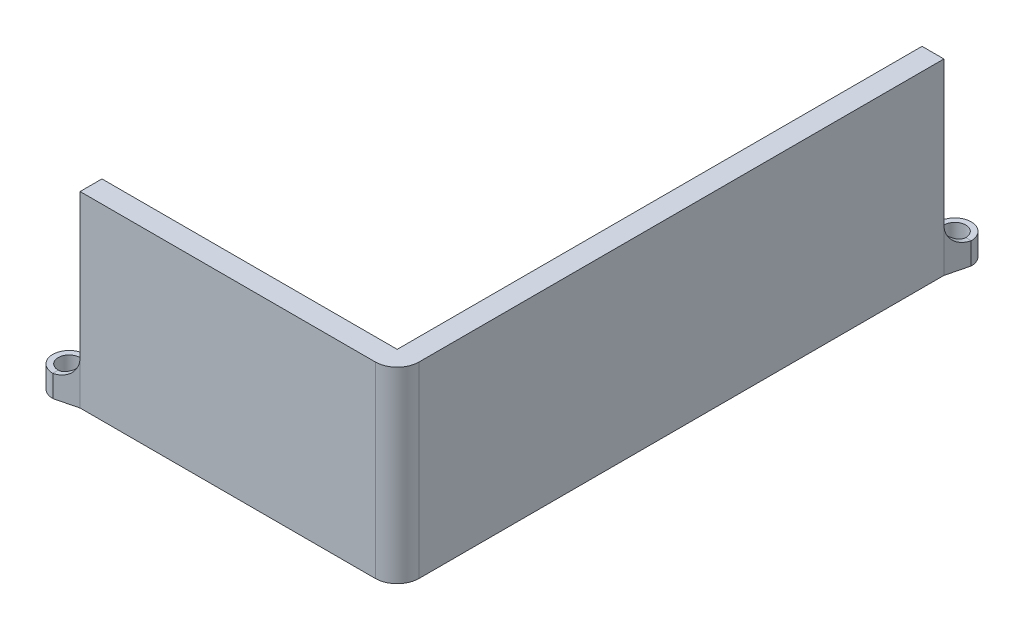
SolidWorks part; units mm, degrees
ref_plane "Front Plane" through (0, 0, 0) normal (0, 0, 1) x (1, 0, 0)
ref_plane "Top Plane" through (0, 0, 0) normal (0, 1, 0) x (1, 0, 0)
ref_plane "Right Plane" through (0, 0, 0) normal (1, 0, 0) x (0, 0, -1)
other "Configuration Table"
sketch "Sketch2" plane through (0, 0, 0) normal (0, 0, 1) x (1, 0, 0)
  line L1 (-13.6181, -8.5) -> (13.3819, -8.5)
  line L2 (-13.6181, -8.5) -> (-13.6181, 8.65)
  line L3 (-13.6181, 8.65) -> (13.3819, 8.65)
  line L4 (13.3819, -8.5) -> (13.3819, 8.65)
  line L5 (11.5, -8.5) -> (-11.5, -8.5) construction
  line L6 (-11.5, 8.5) -> (11.5, 8.5) construction
  line L7 (-13.6181, 8.65) -> (13.3819, -8.5) construction
  point P0 (0, 0)
  dimension "D1" = 27
  dimension "D2" = 0.15
extrude "Boss-Extrude1" add sketch "Sketch2" along normal blind 2
sketch "Sketch3" plane through (13.3819, 0, 0) normal (1, 0, 0) x (0, 0, -1)
  line L1 (-2, 8.65) -> (48, 8.65)
  line L2 (-2, 8.65) -> (-2, -8.5)
  line L3 (-2, -8.5) -> (48, -8.5)
  line L4 (48, 8.65) -> (48, -8.5)
  line L5 (-2, -8.5) -> (0, -8.5) construction
  line L6 (-2, -8.5) -> (0, -8.5)
  line M3 (0, -8.5) -> (0, 8.65)
  line M4 (0, 8.65) -> (-2, 8.65)
  line M5 (-2, 8.65) -> (-2, -8.5)
  line M6 (-2, -8.5) -> (0, -8.5)
  dimension "D1" = 50
extrude "Boss-Extrude2" add sketch "Sketch3" along normal blind 2 contours L4 L1 L3 M3 | M6 M3 M4 M5 region at (13.3819, 0.075, 1) region at (13.3819, 0.075, -24)
fillet "Fillet1" radius 2 1 edges at (15.3819, 0.075, 2)
sketch "Sketch4" plane through (0, -8.5, 0) normal (0, -1, 0) x (1, 0, 0)
  line L0 (14.3819, -48) -> (14.3819, -50) construction
  line L1 (12.8819, -50) -> (13.3819, -48)
  line L2 (15.8819, -50) -> (15.3819, -48)
  line L3 (-15.6181, -0.5) -> (-13.6181, 0)
  line L4 (-15.6181, 2.5) -> (-13.6181, 2)
  line L5 (-15.6181, 1) -> (-13.6181, 1) construction
  line L6 (15.3819, -48) -> (15.3819, 0)
  line L7 (13.3819, 2) -> (-13.6181, 2)
  line L8 (-13.6181, 2) -> (-13.6181, 0)
  line L9 (-13.6181, 0) -> (13.3819, 0)
  line L10 (13.3819, 0) -> (13.3819, -48)
  line L11 (13.3819, -48) -> (15.3819, -48)
  line L12 (15.3819, -48) -> (15.3819, 0)
  line L13 (13.3819, 2) -> (-13.6181, 2)
  line L14 (-13.6181, 2) -> (-13.6181, 0)
  line L15 (-13.6181, 0) -> (13.3819, 0)
  line L16 (13.3819, 0) -> (13.3819, -48)
  line L17 (13.3819, -48) -> (15.3819, -48)
  circle A0 centre (14.3819, -50) radius 1.5
  circle A1 centre (14.3819, -50) radius 1
  circle A2 centre (-15.6181, 1) radius 1.5
  arc A3 (15.3819, 0) -> (13.3819, 2) centre (13.3819, 0) ccw
  arc A4 (15.3819, 0) -> (13.3819, 2) centre (13.3819, 0) ccw
  circle A5 centre (-15.6181, 1) radius 1
  line M13 (-13.6181, 2) -> (-13.6181, 0)
  line M16 (13.3819, -48) -> (15.3819, -48)
  dimension "D1" = 3
  dimension "D2" = 2
  dimension "D4" = 2
  dimension "D5" = 2
  dimension "D3" = 0
extrude "Boss-Extrude3" add sketch "Sketch4" against normal blind 2 contours A0 L2 L1 M16 | L2 A0 L1 A1 | L3 A2 L4 A5 | A2 L3 L4 M13 region at (13.0113, -8.5, -49.6573) region at (14.3819, -8.5, -48.3885) region at (-14.0066, -8.5, 1) region at (-15.2754, -8.5, -0.3706)
fillet "Fillet2" radius 2 2 edges at (-13.6181, -6.5, 1) (14.3819, -6.5, -48)
ref_plane "Plane1" through (0, 0, 2.5) normal (0, 0, 1) x (0, -1, 0)
equation "\"C\"=0.15"
equation "\"D2@Sketch2\"=\"C\""
equation "\"FL\"=2"
equation "\"D4@Sketch4\"=\"FL\""
equation "\"D5@Sketch4\"=\"FL\""
